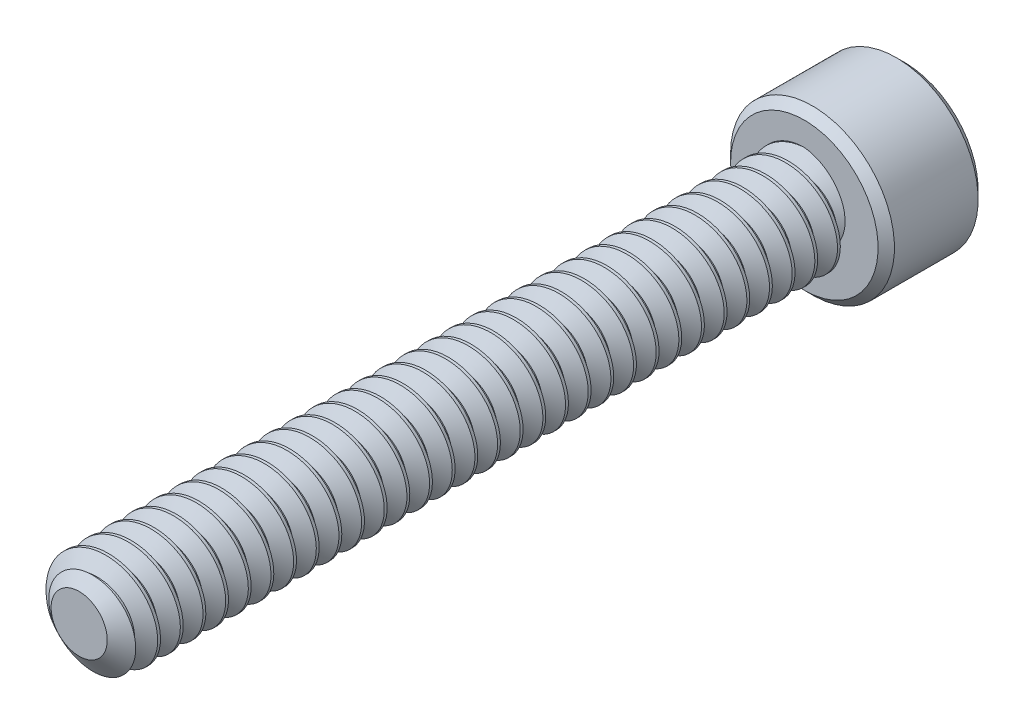
SolidWorks part; units mm, degrees
other "DetailItem1"
ref_plane "Front Plane" through (0, 0, 0) normal (0, 0, 1) x (1, 0, 0)
ref_plane "Top Plane" through (0, 0, 0) normal (0, 1, 0) x (1, 0, 0)
ref_plane "Right Plane" through (0, 0, 0) normal (1, 0, 0) x (0, 0, -1)
sketch "Sketch1" plane through (0, 0, 0) normal (0, 0, 1) x (1, 0, 0)
  circle A0 centre (0, 0) radius 1.7526
  dimension "OD" = 3.5052
extrude "Extrude1" add sketch "Sketch1" against normal blind 25.4
sketch "Sketch2" plane through (0, 0, 0) normal (0, 0, 1) x (1, 0, 0)
  circle A0 centre (0, 0) radius 1.7526 construction
  circle A1 centre (0, 0) radius 1.7526
curve "Helix/Spiral1" pitch 0.7937 height 26.1937 turns 33 parameters "pitch"=0.7937
sketch "Sketch3" plane through (0, 0, 0) normal (1, 0, 0) x (0, 0, -1)
  line L0 (-0.6945, 1.7526) -> (-0.3969, 1.237)
  line L1 (-0.3969, 1.237) -> (-0.2977, 1.237)
  line L2 (-0.2977, 1.237) -> (0, 1.7526)
  line L3 (-0.6945, 1.7526) -> (0, 1.7526)
  line L4 (-0.3473, 1.7526) -> (-0.3473, 1.237) construction
  line L5 (-0.5457, 1.4948) -> (-0.1488, 1.4948) construction
  line L6 (0, 1.7526) -> (0, -1.7526) construction
  dimension "D1" = 0.0992
  dimension "D2" = 0.3969
  dimension "D3" = 60
sweep "Cut-Sweep1" cut profiles "Sketch3" path "Helix/Spiral1"
sketch "Sketch4" plane through (0, 0, 0) normal (1, 0, 0) x (0, 0, -1)
  line L0 (0.5388, 1.7526) -> (0, 0.983)
  line L1 (0, 0.983) -> (0, 1.7526)
  line L2 (0.5388, 1.7526) -> (0, 1.7526)
  line L3 (-0.6945, 1.7526) -> (0, 1.7526) construction
  line L4 (0, 0) -> (7.0209, 0) construction
  dimension "D1" = 55
  dimension "D2" = 0.254
revolve "Cut-Revolve1" cut sketch "Sketch4" angle 360 about L4
sketch "Sketch5" plane through (0, 0, 0) normal (1, 0, 0) x (0, 0, -1)
  line L0 (25.4, -1.2539) -> (25.4, 1.2505) construction
  line L1 (25.4, 1.8796) -> (0.1202, 1.8796)
  line L2 (25.4, 1.8796) -> (25.4, 0)
  line L3 (25.4, 0) -> (0, 0)
  line L4 (0, 1.5494) -> (0, 0)
  line L5 (0.1202, 1.8796) -> (0, 1.5494)
  line L6 (0, 0) -> (9.9695, 0) construction
  point P3 (0, 1.8796)
  point P10 (0, 1.8796)
  dimension "D1" = 0.3302
  dimension "D2" = 0.127
  dimension "D3" = 20
  dimension "Min Thread" = 0
revolve "partially thread" [suppressed] add sketch "Sketch5" angle 360 about L6
sketch "Sketch6" plane through (0, 0, -25.4) normal (0, 0, -1) x (-1, 0, 0)
  circle A0 centre (0, 0) radius 2.8702
  dimension "head dia" = 5.7404
extrude "Extrude2" add sketch "Sketch6" along normal blind 3.5052
sketch "Sketch7" plane through (0, 0, -28.9052) normal (0, 0, -1) x (-1, 0, 0)
  line L1 (0, 1.604) -> (-1.3891, 0.802)
  line L2 (-1.3891, 0.802) -> (-1.3891, -0.802)
  line L3 (-1.3891, -0.802) -> (0, -1.604)
  line L4 (0, -1.604) -> (1.3891, -0.802)
  line L5 (1.3891, -0.802) -> (1.3891, 0.802)
  line L6 (1.3891, 0.802) -> (0, 1.604)
  circle A0 centre (0, 0) radius 1.3891 construction
  dimension "hex dia" = 2.7781
extrude "Cut-Extrude1" cut sketch "Sketch7" against normal blind 2.0836
sketch "Sketch8" plane through (0, 0, -28.9052) normal (0, 0, -1) x (-1, 0, 0)
  circle A0 centre (0, 0) radius 1.604
extrude "Cut-Extrude2" cut sketch "Sketch8" against normal through all draft 45
chamfer "Chamfer1" distance 0.287 angle 45 2 edges at (-2.8702, 0, -28.9052) (-2.8702, 0, -25.4)
sketch "Sketch9" plane through (0, 0, 0) normal (1, 0, 0) x (0, 0, -1)
  line L0 (0, 1.7526) -> (0, -1.7526) construction
  line L1 (1.9844, 1.7526) -> (1.9844, -1.7526) construction
  dimension "D1" = 1.9844
equation "\"D3@Helix/Spiral1\" = \"screw length@Extrude1\"+\"pitch@Helix/Spiral1\""
equation "\"D1@Sketch3\" = \"pitch@Helix/Spiral1\"*.125"
equation "\"D2@Sketch3\" = \"pitch@Helix/Spiral1\"*.5"
equation "\"D1@Cut-Extrude1\" = \"hex dia@Sketch7\"*.75"
equation "\"D1@Chamfer1\" = \"head dia@Sketch6\"*.05"
equation "\"D1@Sketch9\" = \"pitch@Helix/Spiral1\"*2.5"
